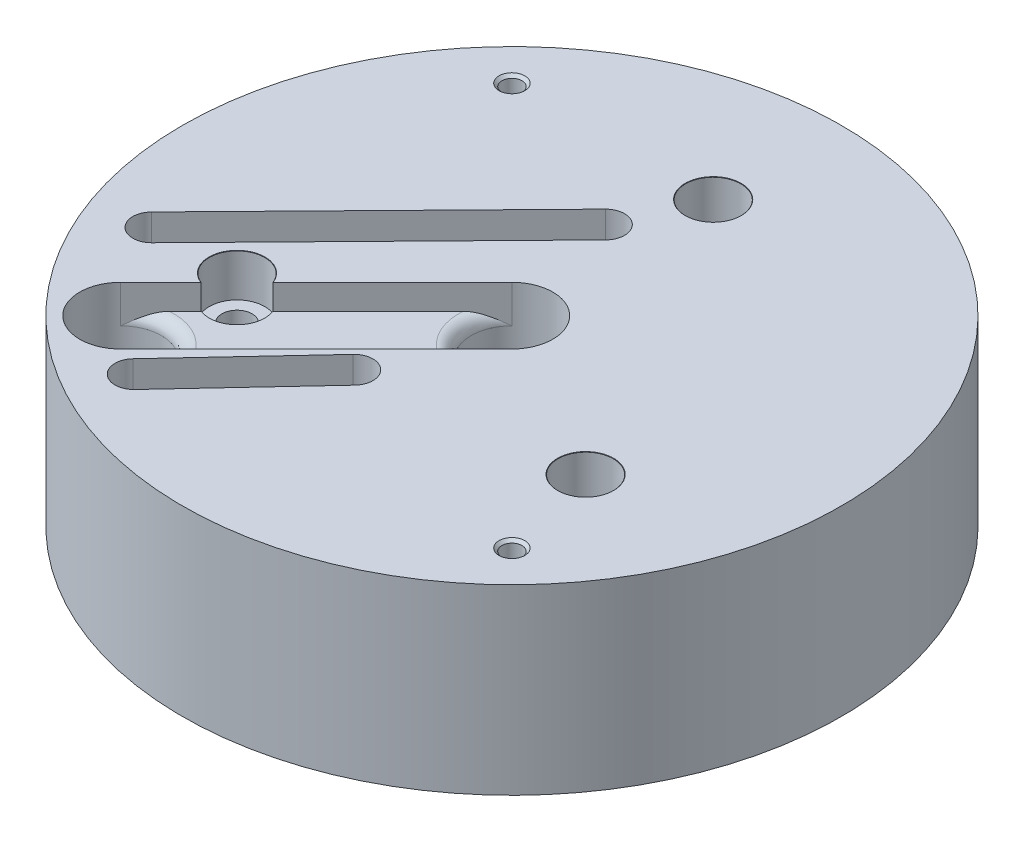
SolidWorks part; units mm, degrees
note: '?' marks a value the reader was unsure of.
ref_plane "Front Plane" through (0, 0, 0) normal (0, 0, 1) x (1, 0, 0)
ref_plane "Top Plane" through (0, 0, 0) normal (0, 1, 0) x (1, 0, 0)
ref_plane "Right Plane" through (0, 0, 0) normal (1, 0, 0) x (0, 0, -1)
sketch "Sketch1" plane through (0, 0, 0) normal (0, 0, 1) x (1, 0, 0)
  line L0 (0, 78.4471) -> (0, -76.9705) construction
  line L1 (-83.0616, 0) -> (77.155, 0) construction
  line L3 (-27, 27) -> (27, 27)
  line L4 (-27, 27) -> (-27, -27)
  line L5 (-27, -27) -> (27, -27)
  line L6 (27, 27) -> (27, -27)
  dimension "D1" = 54
  dimension "D2" = 54
extrude "Boss-Extrude1" add sketch "Sketch1" along normal blind 54
ref_plane "Plane1" through (0, -13.5, 13.5) normal (0, -0.7071, 0.7071) x (1, 0, 0)
ref_axis "Axis1" through (-27, 27, 54) along (0.5774, -0.5774, -0.5774)?
ref_plane "Plane2" through (0, 0, 0) normal (-0.5774, -0.5774, 0.5774) x (0.8165, -0.4082, 0.4082)
ref_plane "Plane3" through (-18, -18, 18) normal (0.5774, 0.5774, -0.5774) x (-0.8165, 0.4082, -0.4082)
ref_plane "Plane4" through (-9, -9, 9) normal (-0.5774, -0.5774, 0.5774) x (0.8165, -0.4082, 0.4082)
ref_plane "Plane10" through (0, 10, 0) normal (0, 1, 0) x (1, 0, 0)
sketch "Sketch2" plane through (-2.0455, 10, 2.0455) normal (0, -1, 0) x (0.9659, 0, 0.2588)
  line L1 (73.4206, 63.196) -> (-42.9368, 63.196)
  line L2 (73.4206, 63.196) -> (73.4206, -31.2358)
  line L3 (73.4206, -31.2358) -> (-42.9368, -31.2358)
  line L4 (-42.9368, 63.196) -> (-42.9368, -31.2358)
extrude "Cut-Extrude1" cut sketch "Sketch2" against normal blind 2.5 and the other way through all
ref_plane "Plane5" through (0, 27, 0) normal (0, -1, 0) x (0.9659, 0, 0.2588)
ref_plane "Plane12" through (0, 0, 27) normal (0, 0, 1) x (1, 0, 0)
sketch "Sketch3" plane through (0, 12.5, 0) normal (0, -1, 0) x (0.2588, 0, 0.9659)
  line L0 (60.4997, 16.2109) -> (-22.3999, -6.002) construction
  line L1 (59.1481, -12.1038) -> (45.1719, 40.0562) construction
  line L2 (59.1481, -12.1038) -> (6.9881, -26.08) construction
  line L3 (-6.9881, 26.08) -> (45.1719, 40.0562) construction
  line L4 (13.6745, 53.286) -> (38.4028, -39.0013) construction
  line L5 (6.9881, -26.08) -> (-6.9881, 26.08) construction
  circle A0 centre (26.08, 6.9881) radius 17.75
  dimension "D1" = 35.5
extrude "Cut-Extrude2" cut sketch "Sketch3" against normal offset from surface (6.75 mm away) 9.25 up to plane "Plane10"
sketch "Sketch4" plane through (0, 12.5, 0) normal (0, -1, 0) x (0.2588, 0, 0.9659)
  circle A0 centre (26.08, 6.9881) radius 3.25
  dimension "D1" = 6.5
extrude "Cut-Extrude3" cut sketch "Sketch4" against normal through all
sketch "Sketch5" plane through (0, 12.5, 0) normal (0, -1, 0) x (0.2588, 0, 0.9659)
  circle A0 centre (26.08, 6.9881) radius 24
  dimension "D1" = 48
sketch "Sketch7" plane through (0, 27, 0) normal (0, -1, 0) x (0.9659, 0, 0.2588)
  circle A0 centre (6.9881, 26.08) radius 3.25
  dimension "D1" = 6.5
sketch "Sketch8" plane through (0, 27, 0) normal (0, -1, 0) x (0.9659, 0, 0.2588)
  line L1 (-42.041, 82.4479) -> (65.64, 82.4479)
  line L2 (-42.041, 82.4479) -> (-42.041, -36.5378)
  line L3 (-42.041, -36.5378) -> (65.64, -36.5378)
  line L4 (65.64, 82.4479) -> (65.64, -36.5378)
sketch "Sketch9" plane through (0, 19.25, 0) normal (0, -1, 0) x (0.2588, 0, 0.9659)
  circle A0 centre (26.08, 6.9881) radius 5.5
  dimension "D1" = 11
extrude "Cut-Extrude7" cut sketch "Sketch9" against normal blind 2
ref_axis "Axis4" through (0, 27, 27) along (0, -1, 0)?
sketch "Sketch21" plane through (0, 12.5, 0) normal (0, -1, 0) x (0.2588, 0, 0.9659)
  circle A0 centre (26.08, 6.9881) radius 34.25
  circle A1 centre (26.08, 6.9881) radius 45
  dimension "D1" = 90
  dimension "D2" = 68.5
hole_wizard "M2 Tapped Hole4" positions "Sketch26" profile "Sketch27" tap size "M2" standard "KS"
sketch "Sketch26" plane through (0, 27, 0) normal (0, 1, 0) x (1, 0, 0)
  circle A0 centre (0, -27) radius 3.25 construction
  point P0 (-16, -11)
  point P2 (16, -43)
  dimension "D1" = 16
  dimension "D2" = 16
  dimension "D3" = 16
  dimension "D4" = 16
sketch "Sketch27" plane through (-16, 27, 11) normal (1, 0, 0) x (0, 0, 1)
  line L0 (0, 0) -> (0, 7.4807)
  line L1 (0, 7.4807) -> (0.8, 7)
  line L2 (0.8, 7) -> (0.8, 0.225)
  line L3 (0.8, 0.225) -> (1.025, 0)
  line L5 (1.025, 0) -> (0, 0)
  line L6 (-0.8, 0.225) -> (-1.025, 0) construction
  line L10 (0, 7.4807) -> (-0.8, 7) construction
  line L11 (0, -6.35) -> (0, 107.95) construction
  dimension "Tap Drill Dia." = 1.6
  dimension "Tap Drill Depth" = 7
  dimension "Near C'Sink Dia." = 2.05
  dimension "Near C'Sink Angle" = 90
  dimension "Drill Angle" = 118
cosmetic thread "Hole Thread4" parameters "D1"=5, "D2"=2
cosmetic thread "Hole Thread5" parameters "D1"=5, "D2"=2
hole_wizard "Ø6.5 (6.5) Diameter Hole1" positions "Sketch29" profile "Sketch31" hole size "Ø6.5" standard "ISO" end condition through all
sketch "Sketch29" plane through (0, 27, 0) normal (0, 1, 0) x (1, 0, 0)
  line L0 (0, -76.3534) -> (0, 25.0171) construction
  line L2 (0, -27) -> (-39.9605, -66.9605) construction
  point P0 (-15.5563, -42.5563)
  dimension "D1" = 22
  dimension "D2" = 45
sketch "Sketch31" plane through (-15.5563, 27, 42.5563) normal (1, 0, 0) x (0, 0, 1)
  line L0 (0, 0) -> (0, 14.5)
  line L1 (0, 14.5) -> (3.25, 14.5)
  line L2 (3.25, 14.5) -> (3.25, 0)
  line L5 (3.25, 0) -> (0, 0)
  line L11 (0, -6.35) -> (0, 107.95) construction
  dimension "Thru Hole Dia." = 6.5
  dimension "Thru Hole Depth" = 14.5
sketch "Sketch32" plane through (0, 27, 0) normal (0, 1, 0) x (1, 0, 0)
  line L0 (2.2981, -29.2981) -> (-13.2583, -44.8544)
  line L1 (-2.2981, -24.7019) -> (-17.8544, -40.2583)
  line L2 (2.2981, -29.2981) -> (-2.2981, -24.7019)
  line L3 (-13.2583, -44.8544) -> (-17.8544, -40.2583)
  circle A1 centre (-15.5563, -42.5563) radius 3.25 construction
  circle A2 centre (0, -27) radius 3.25 construction
extrude "Cut-Extrude10" cut sketch "Sketch32" against normal blind 2
fillet "Fillet2" radius 1 3 edges at (-13.2583, 25, 40.2583) (-2.2981, 25, 29.2981) (0, 21.25, 23.75)
hole_wizard "CBORE SLOT for M2 Cheese Head Screw2" positions "Sketch33" profile "Sketch34" size "M2" standard "ISO" slot yes end condition through all
sketch "Sketch33" plane through (0, 27, 0) normal (0, 1, 0) x (1, 0, 0)
  line L0 (0, -27) -> (0, 14.6936) construction
  point P0 (0, -11)
  dimension "D1" = 16
sketch "Sketch34" plane through (0, 27, 11) normal (1, 0, 0) x (0, 0, 1)
  line L0 (0, 0) -> (0, 14.5)
  line L1 (0, 14.5) -> (1.2, 14.5)
  line L3 (1.2, 14.5) -> (1.2, 3.4)
  line L4 (2.2, 3.4) -> (1.2, 3.4)
  line L5 (2.2, 3.4) -> (2.2, 0.025)
  line L6 (2.2, 0.025) -> (2.225, 0)
  line L7 (2.225, 0) -> (0, 0)
  line L8 (-2.2, 0.025) -> (-2.225, 0) construction
  line L11 (0, -6.35) -> (0, 107.95) construction
  dimension "Thru Hole Dia." = 2.4
  dimension "Thru Hole Depth" = 14.5
  dimension "C'Bore Dia." = 4.4
  dimension "C'Bore Depth" = 3.4
  dimension "Near C'Sink Dia." = 4.45
  dimension "Near C'Sink Angle" = 90
pattern_circular "CirPattern2" count 3 every 120 about axis through (0, 0, 27) along (0, 1, 0) of "CBORE SLOT for M2 Cheese Head Screw2"
sketch "Sketch36" plane through (0, 12.5, 0) normal (0, -1, 0) x (1, 0, 0)
  line L0 (27, 0) -> (-27, 0) construction
  circle A0 centre (0, 27) radius 27
  circle A1 centre (0, 27) radius 38.7941
extrude "Cut-Extrude11" cut sketch "Sketch36" against normal blind 1
hole_wizard "Ø3.0mm Dowel Hole1" positions "Sketch37" profile "Sketch38" hole size "Ø3.0" standard "ISO" end condition through all
sketch "Sketch37" plane through (0, 27, 0) normal (0, 1, 0) x (1, 0, 0)
  line L1 (0, -27) -> (-19.4966, -60.7691) construction
  line L2 (0, -7.975) -> (0, 7.975) construction
  line L3 (0, -27) -> (-32.4822, -40.1237) construction
  arc A0 (2.2981, -29.2981) -> (-2.2981, -24.7019) centre (0, -27) ccw construction
  circle A1 centre (0, -27) radius 3.25 construction
  point P0 (-11, -46.0526)
  point P2 (-20.398, -35.2413)
  dimension "D1" = 22
  dimension "D2" = 22
  dimension "D3" = 30
  dimension "D4" = 68
sketch "Sketch38" plane through (-11, 27, 46.0526) normal (1, 0, 0) x (0, 0, 1)
  line L0 (0, 0) -> (0, 14.5)
  line L1 (0, 14.5) -> (1.5, 14.5)
  line L2 (1.5, 14.5) -> (1.5, 0)
  line L5 (1.5, 0) -> (0, 0)
  line L11 (0, -6.35) -> (0, 107.95) construction
  dimension "Thru Hole Dia." = 3
  dimension "Thru Hole Depth" = 14.5
sketch "Sketch39" plane through (0, 27, 0) normal (0, 1, 0) x (1, 0, 0)
  line L0 (-2.55, -37) -> (-11, -46.0526) construction
  line L1 (-1.4535, -38.0235) -> (-9.9035, -47.0761)
  line L2 (-3.6465, -35.9765) -> (-12.0965, -45.029)
  line L3 (-2.55, -17) -> (-20.398, -35.2413) construction
  line L4 (-1.4778, -18.049) -> (-19.3259, -36.2904)
  line L5 (-3.6222, -15.951) -> (-21.4702, -34.1923)
  line L6 (0, -7.975) -> (0, 7.975) construction
  line L7 (-7.975, -27) -> (7.975, -27) construction
  arc A0 (-1.4535, -38.0235) -> (-3.6465, -35.9765) centre (-2.55, -37) ccw
  arc A1 (-12.0965, -45.029) -> (-9.9035, -47.0761) centre (-11, -46.0526) ccw
  arc A2 (-1.4778, -18.049) -> (-3.6222, -15.951) centre (-2.55, -17) ccw
  arc A3 (-21.4702, -34.1923) -> (-19.3259, -36.2904) centre (-20.398, -35.2413) ccw
  point P3 (-6.775, -41.5263)
  point P8 (-11.474, -26.1207)
  dimension "D1" = 2.55
  dimension "D2" = 2.55
  dimension "D3" = 10
  dimension "D4" = 10
  dimension "D5" = 3
  dimension "D6" = 3
extrude "Cut-Extrude12" cut sketch "Sketch39" against normal blind 3
sketch "Sketch40" plane through (0, 27, 0) normal (0, 1, 0) x (1, 0, 0)
  circle A0 centre (0, -27) radius 26.2
  dimension "D1" = 52.4
extrude "Cut-Extrude13" cut sketch "Sketch40" against normal through all flip side to cut
sketch "Sketch41" plane through (0, 27, 0) normal (0, 1, 0) x (1, 0, 0)
  line L0 (-15.5563, -42.5563) -> (-23.5653, -38.4506)
  circle A0 centre (-15.5563, -42.5563) radius 9
  circle A1 centre (0, -27) radius 26.2
  dimension "D1" = 18
  dimension "D2" = 52.4
sketch3d "3DSketch1"
  line L0 (-23.5653, 27, 38.4506) -> (-23.5653, 20.53, 38.4506)
  point P3 (0, 0, 0)
  dimension "D1" = 6.47
ref_plane "Plane13" through (-20.5134, 0, 40.0152) normal (-0.4562, 0, 0.8899) x (0.8899, 0, 0.4562)
ref_plane "Plane14" through (-3.0519, 0, -1.5645) normal (-0.8899, 0, -0.4562) x (0, -1, 0)
sketch3d "3DSketch2"
  line L0 (-26.0042, 20.1845, 37.2004) -> (-23.5432, 20.1845, 38.4619)
  point P2 (0, 0, 0)
ref_plane "Plane15" through (-5.4908, 0, -2.8148) normal (0.8899, 0, 0.4562) x (0.4562, 0, -0.8899)
hole_wizard "Ø2.0mm Dowel Hole8" positions "Sketch53" profile "Sketch54" hole size "Ø2.0" standard "ISO"
sketch "Sketch53" plane through (-5.4908, 0, -2.8148) normal (0.8899, 0, 0.4562) x (0.4562, 0, -0.8899)
  point P0 (-44.9668, 20.53)
sketch "Sketch54" plane through (-26.0042, 20.53, 37.2004) normal (0, 1, 0) x (-0.4562, 0, 0.8899)
  line L0 (0, 0) -> (0, 8.4907)
  line L1 (0, 8.4907) -> (1, 8.4907)
  line L2 (1, 8.4907) -> (1, 0)
  line L5 (1, 0) -> (0, 0)
  line L11 (0, -6.35) -> (0, 107.95) construction
  dimension "Thru Hole Dia." = 2
  dimension "Thru Hole Depth" = 8.4907
